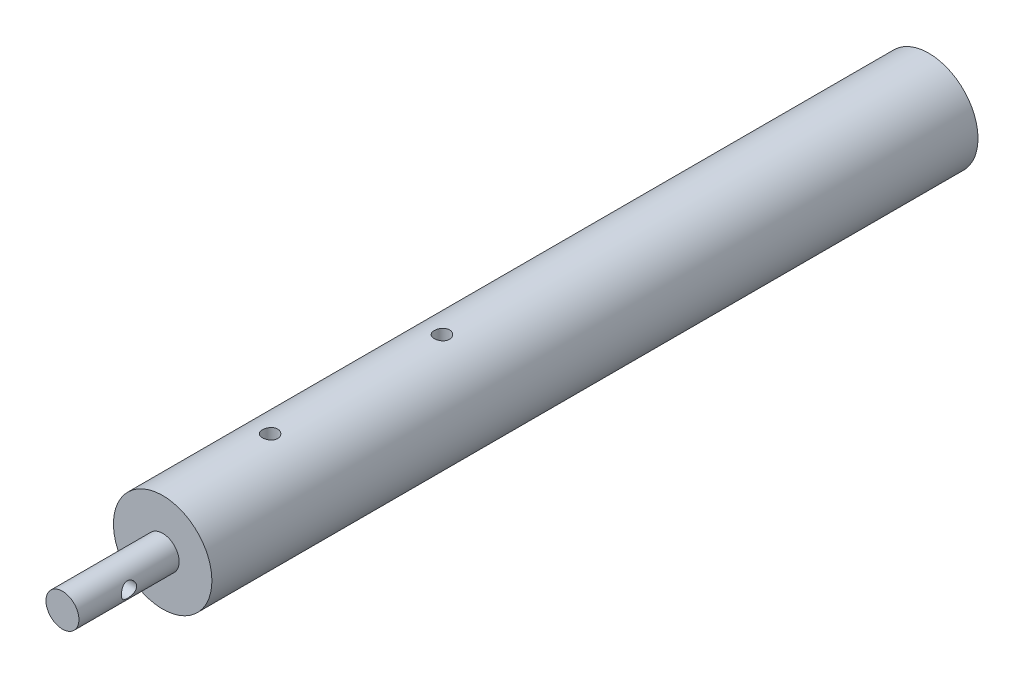
SolidWorks part; units mm, degrees
ref_plane "Front Plane" through (0, 0, 0) normal (0, 0, 1) x (1, 0, 0)
ref_plane "Top Plane" through (0, 0, 0) normal (0, 1, 0) x (1, 0, 0)
ref_plane "Right Plane" through (0, 0, 0) normal (1, 0, 0) x (0, 0, -1)
sketch "Sketch1" plane through (0, 0, 0) normal (0, 0, 1) x (1, 0, 0)
  circle A0 centre (0, 0) radius 8.7312
  dimension "D1" = 17.4625
extrude "Boss-Extrude1" add sketch "Sketch1" along normal blind 135.89
sketch "Sketch2" plane through (0, 0, 135.89) normal (0, 0, 1) x (1, 0, 0)
  circle A0 centre (0, 0) radius 2.921
  dimension "D1" = 5.842
extrude "Boss-Extrude2" add sketch "Sketch2" along normal blind 17.78
ref_plane "Plane1" through (0, 8.7312, 0) normal (0, 1, 0) x (1, 0, 0)
sketch "Sketch4" plane through (0, 8.7312, 0) normal (0, 1, 0) x (1, 0, 0)
  line L1 (-2.921, -153.67) -> (2.921, -153.67) construction
  circle A0 centre (0, -86.36) radius 1.8415
  circle A1 centre (0, -116.84) radius 1.8415
  dimension "D1" = 3.683
  dimension "D2" = 67.31
  dimension "D3" = 36.83
hole_wizard "#6-32 Tapped Hole1" positions "Sketch5" profile "Sketch6" tap size "#6-32" standard "ANSI Inch" end condition through all
sketch "Sketch5" plane through (0, 8.7312, 0) normal (0, 1, 0) x (1, 0, 0)
  point P0 (0, -86.36)
  point P3 (0, -116.84)
sketch "Sketch6" plane through (0, 8.7312, 86.36) normal (1, 0, 0) x (0, 0, 1)
  line L0 (0, 0) -> (0, 17.4625)
  line L1 (0, 17.4625) -> (1.3525, 17.4625)
  line L2 (1.3525, 17.4625) -> (1.3525, 0)
  line L5 (1.3525, 0) -> (0, 0)
  line L11 (0, -6.35) -> (0, 107.95) construction
  dimension "Thru Tap Drill Dia." = 2.7051
  dimension "Thru Tap Drill Depth" = 17.4625
cosmetic thread "Hole Thread1" parameters "D2"=3.5052
cosmetic thread "Hole Thread2" parameters "D2"=3.5052
ref_plane "Plane2" through (2.921, 0, 0) normal (1, 0, 0) x (0, 0, -1)
sketch "Sketch7" plane through (2.921, 0, 0) normal (1, 0, 0) x (0, 0, -1)
  line L1 (-153.67, 2.921) -> (-153.67, -2.921) construction
  circle A0 centre (-144.78, 0) radius 1.8415
  dimension "D1" = 3.683
  dimension "D2" = 8.89
hole_wizard "#6-32 Tapped Hole2" positions "Sketch8" profile "Sketch9" tap size "#6-32" standard "ANSI Inch" end condition through all
sketch "Sketch8" plane through (2.921, 0, 0) normal (1, 0, 0) x (0, 0, -1)
  point P0 (-144.78, 0)
sketch "Sketch9" plane through (2.921, 0, 144.78) normal (0, 1, 0) x (0, 0, -1)
  line L0 (0, 0) -> (0, 11.6522)
  line L1 (0, 11.6522) -> (1.3525, 11.6522)
  line L2 (1.3525, 11.6522) -> (1.3525, 0)
  line L5 (1.3525, 0) -> (0, 0)
  line L11 (0, -6.35) -> (0, 107.95) construction
  dimension "Thru Tap Drill Dia." = 2.7051
  dimension "Thru Tap Drill Depth" = 11.6522
cosmetic thread "Hole Thread3" parameters "D2"=3.5052
